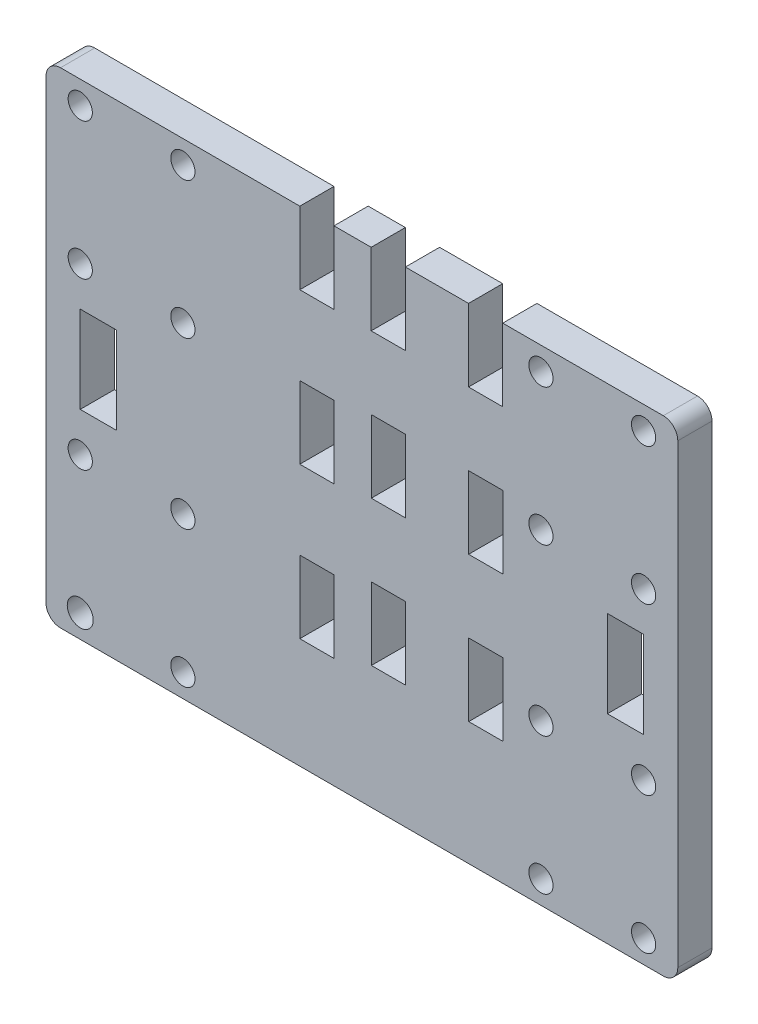
SolidWorks part; units mm, degrees
ref_plane "Front Plane" through (0, 0, 0) normal (0, 0, 1) x (1, 0, 0)
ref_plane "Top Plane" through (0, 0, 0) normal (0, 1, 0) x (1, 0, 0)
ref_plane "Right Plane" through (0, 0, 0) normal (1, 0, 0) x (0, 0, -1)
sketch "Sketch1" plane through (0, 0, 0) normal (0, 0, 1) x (1, 0, 0)
  line L0 (333.6594, 144.0694) -> (339.6538, 144.0694)
  line L1 (375.975, 144.0694) -> (270.255, 144.0694)
  line L2 (378.515, 146.6094) -> (378.515, 226.6327)
  line L3 (270.2574, 229.1713) -> (312.2247, 229.1314)
  line L4 (267.715, 146.6094) -> (267.715, 226.6313)
  line L5 (318.2191, 229.1365) -> (324.7384, 229.1406)
  line L6 (347.8135, 229.1551) -> (375.9734, 229.1727)
  line L7 (330.7408, 229.1406) -> (341.8152, 229.1551)
  line L8 (324.7384, 229.1406) -> (324.7384, 216.4444)
  line L9 (324.7384, 216.4444) -> (330.7408, 216.4444)
  line L10 (330.7408, 229.1406) -> (330.7408, 216.4444)
  line L11 (330.7487, 203.7444) -> (324.7623, 203.7444)
  line L12 (330.7487, 203.7444) -> (330.7487, 191.0406)
  line L13 (330.7487, 191.0406) -> (324.7623, 191.0406)
  line L14 (324.7623, 203.7444) -> (324.7623, 191.0406)
  line L15 (330.7646, 178.3444) -> (324.7782, 178.3444)
  line L16 (330.7646, 178.3444) -> (330.7646, 165.6406)
  line L17 (330.7646, 165.6406) -> (324.7782, 165.6406)
  line L19 (312.2247, 216.4314) -> (318.2191, 216.4314)
  line L20 (312.2247, 216.4314) -> (312.2247, 229.1365)
  line L21 (312.2247, 229.1365) -> (318.2191, 229.1365)
  line L22 (318.2191, 216.4314) -> (318.2191, 229.1365)
  line L23 (312.2247, 202.6314) -> (318.2191, 202.6314)
  line L24 (312.2247, 202.6314) -> (312.2247, 189.9314)
  line L25 (312.2247, 189.9314) -> (318.2191, 189.9314)
  line L26 (318.2191, 202.6314) -> (318.2191, 189.9314)
  line L27 (312.2247, 176.1314) -> (318.2191, 176.1314)
  line L28 (324.7782, 178.3444) -> (324.7782, 165.6406)
  line L29 (312.2247, 176.1314) -> (312.2247, 163.4314)
  line L30 (341.847, 165.6513) -> (347.8334, 165.6513)
  line L31 (341.847, 165.6513) -> (341.847, 178.3551)
  line L32 (341.847, 178.3551) -> (347.8334, 178.3551)
  line L33 (347.8334, 165.6513) -> (347.8334, 178.3551)
  line L34 (341.8311, 191.0513) -> (347.8175, 191.0513)
  line L35 (273.7094, 186.6203) -> (273.7094, 194.2403)
  line L36 (273.7094, 194.2403) -> (280.0594, 194.2403)
  line L37 (280.0594, 194.2403) -> (280.0594, 179.0003)
  line L38 (280.0594, 179.0003) -> (273.7094, 179.0003)
  line L39 (273.7094, 179.0003) -> (273.7094, 186.6203)
  line L40 (372.5206, 179.0003) -> (372.5206, 186.6203)
  line L41 (366.1706, 179.0003) -> (372.5206, 179.0003)
  line L42 (366.1706, 194.2403) -> (366.1706, 179.0003)
  line L43 (372.5206, 194.2403) -> (366.1706, 194.2403)
  line L44 (372.5206, 186.6203) -> (372.5206, 194.2403)
  line L45 (341.8311, 191.0513) -> (341.8311, 203.7551)
  line L46 (341.8311, 203.7551) -> (347.8175, 203.7551)
  line L47 (347.8175, 191.0513) -> (347.8175, 203.7551)
  line L48 (341.8152, 216.4513) -> (347.8135, 216.4513)
  line L49 (341.8152, 216.4513) -> (341.8152, 229.1551)
  line L50 (341.8152, 229.1551) -> (341.8152, 216.4513)
  line L51 (347.8135, 216.4513) -> (347.8135, 229.1551)
  line L52 (312.2247, 163.4314) -> (318.2191, 163.4314)
  line L53 (341.8311, 203.7551) -> (347.8175, 203.7551)
  line L54 (341.8311, 203.7551) -> (341.8311, 191.0513)
  line L55 (341.8311, 191.0513) -> (347.8175, 191.0513)
  line L56 (347.8175, 203.7551) -> (347.8175, 191.0513)
  line L57 (341.847, 178.3551) -> (347.8334, 178.3551)
  line L58 (341.847, 178.3551) -> (341.847, 165.6513)
  line L59 (341.847, 165.6513) -> (347.8334, 165.6513)
  line L60 (347.8334, 178.3551) -> (347.8334, 165.6513)
  line L61 (324.7782, 178.3444) -> (330.7646, 178.3444)
  line L62 (324.7782, 178.3444) -> (324.7782, 165.6406)
  line L63 (324.7782, 165.6406) -> (330.7646, 165.6406)
  line L64 (330.7646, 178.3444) -> (330.7646, 165.6406)
  line L65 (324.7623, 191.0406) -> (330.7487, 191.0406)
  line L66 (324.7623, 191.0406) -> (324.7623, 203.7444)
  line L67 (324.7623, 203.7444) -> (330.7487, 203.7444)
  line L68 (330.7487, 191.0406) -> (330.7487, 203.7444)
  line L69 (324.7384, 216.4444) -> (330.7408, 216.4444)
  line L70 (324.7384, 216.4444) -> (324.7384, 229.1406)
  line L71 (318.2191, 176.1314) -> (318.2191, 163.4314)
  line L72 (330.7408, 216.4444) -> (330.7408, 229.1406)
  line L74 (341.8152, 229.1551) -> (341.8152, 216.4513)
  line L75 (341.8152, 216.4513) -> (347.8135, 216.4513)
  line L76 (347.8135, 229.1551) -> (347.8135, 216.4513)
  circle A0 centre (372.515, 148.1123) radius 2.125
  circle A1 centre (354.515, 148.1123) radius 2.125
  circle A2 centre (372.515, 172.1123) radius 2.125
  circle A3 centre (354.515, 172.1123) radius 2.125
  circle A4 centre (291.715, 148.1123) radius 2.125
  circle A5 centre (273.715, 148.1123) radius 2.2816
  circle A6 centre (291.715, 172.1123) radius 2.125
  circle A7 centre (273.715, 172.1123) radius 2.125
  circle A8 centre (372.515, 201.1314) radius 2.125
  circle A9 centre (354.515, 201.1314) radius 2.125
  circle A10 centre (372.515, 225.1314) radius 2.125
  circle A11 centre (354.515, 225.1314) radius 2.125
  circle A12 centre (291.715, 201.1314) radius 2.125
  circle A13 centre (273.715, 201.1314) radius 2.125
  circle A14 centre (291.715, 225.1314) radius 2.125
  circle A15 centre (273.715, 225.1314) radius 2.125
  arc A16 (378.515, 226.6327) -> (375.9734, 229.1727) centre (375.975, 226.6327) ccw
  arc A17 (270.2574, 229.1713) -> (267.715, 226.6313) centre (270.255, 226.6313) ccw
  arc A18 (270.255, 144.0694) -> (267.715, 146.6094) centre (270.255, 146.6094) cw
  arc A19 (375.975, 144.0694) -> (378.515, 146.6094) centre (375.975, 146.6094) ccw
  dimension "D1" = 2.54
  dimension "D2" = 2.54
  dimension "D3" = 2.54
  dimension "D4" = 2.54
extrude "Boss-Extrude1" add sketch "Sketch1" along normal blind 5.9944 contours L4 L1 L0 L2 A15 A14 A13 A12 A11 A10 A9 A8 A7 A6 A5 A4 A3 A2 A1 A0 region at (322.6223, 185.7617, 0)
